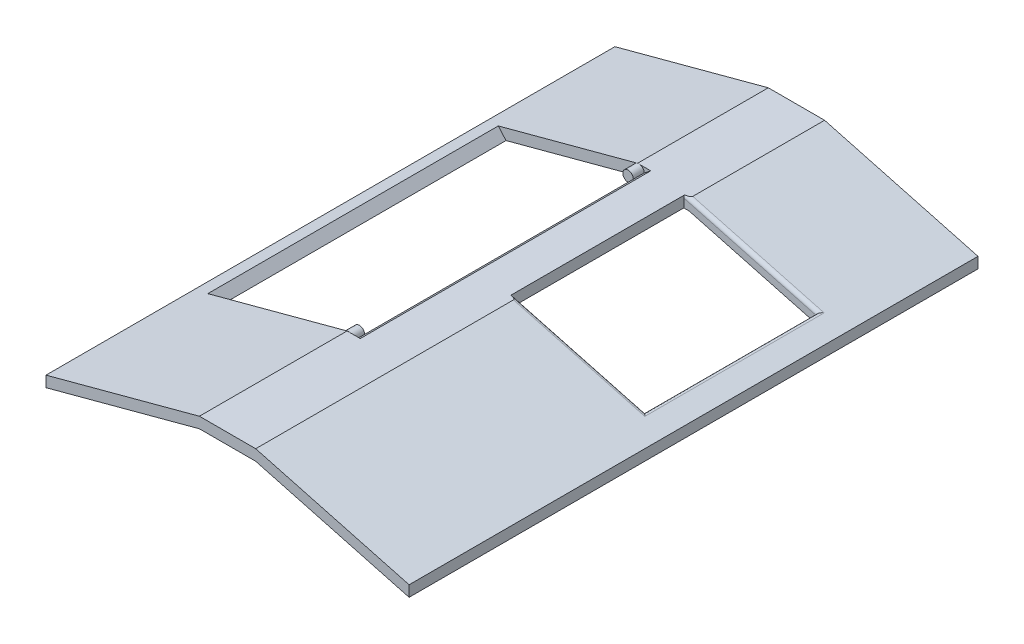
SolidWorks part; units mm, degrees
material "Titan"
ref_plane "Ebene vorne" through (0, 0, 0) normal (0, 0, 1) x (1, 0, 0)
ref_plane "Ebene oben" through (0, 0, 0) normal (0, 1, 0) x (1, 0, 0)
ref_plane "Ebene rechts" through (0, 0, 0) normal (1, 0, 0) x (0, 0, -1)
sketch "Skizze1" plane through (0, 0, 0) normal (0, 0, 1) x (1, 0, 0)
  line L0 (650.3605, 174.2211) -> (650.3605, 144.2211)
  line L5 (650.3605, 144.2211) -> (227.8605, 257.4296)
  line L6 (227.8605, 257.4296) -> (72.8605, 257.4296)
  line L7 (72.8605, 257.4296) -> (-349.6395, 144.2211)
  line L8 (-349.6395, 144.2211) -> (-349.6395, 174.2211)
  line L9 (-349.6395, 174.2211) -> (72.8605, 287.4296)
  line L10 (72.8605, 287.4296) -> (227.8605, 287.4296)
  line L11 (227.8605, 287.4296) -> (650.3605, 174.2211)
  point P0 (0, 0)
  point P7 (650.3605, 159.2211)
  dimension "D1" = 105
  dimension "D2" = 1000
  dimension "D3" = 155
  dimension "D4" = 30
extrude "Aufsatz-Linear austragen1" add sketch "Skizze1" along normal blind 1566.7
sketch "Skizze2" plane through (0, 287.4296, 0) normal (0, 1, 0) x (1, 0, 0)
  line L0 (227.8605, 0) -> (72.8605, 0) construction
  line L1 (145.3605, -360) -> (-289.4795, -360)
  line L2 (145.3605, -360) -> (145.3605, -1160)
  line L3 (145.3605, -1160) -> (-289.4795, -1160)
  line L4 (-289.4795, -360) -> (-289.4795, -1160)
  line L5 (150.3605, -3666.9697) -> (150.3605, -1453.7419) construction
  line L7 (213.1005, -373) -> (577.1205, -373)
  line L8 (213.1005, -373) -> (213.1005, -847)
  line L9 (213.1005, -847) -> (577.1205, -847)
  line L10 (577.1205, -373) -> (577.1205, -847)
  point P14 (150.3605, 0)
  dimension "D1" = 360
  dimension "D2" = 5
  dimension "D3" = 800
  dimension "D4" = 434.84
  dimension "D5" = 474
  dimension "D6" = 364.02
  dimension "D7" = 62.74
  dimension "D8" = 373
extrude "Schnitt-Linear austragen1" cut sketch "Skizze2" against normal up to next
chamfer "Fase1" distance 22 distance2 30 1 edges at (-289.4795, 190.3409, 760) first distance on face at (-123.3495, 234.8553, 771.675)
fillet "Verrundung1" radius 10 3 edges at (402.4905, 240.6377, 373) (577.1205, 193.8457, 610) (402.4905, 240.6377, 847)
sketch "Skizze4" plane through (0, 0, 1160) normal (0, 0, -1) x (-1, 0, 0)
  line L4 (-37.3835, 247.9236) -> (-108.3409, 266.9366) construction
  line L5 (-72.8605, 257.4296) -> (289.4795, 160.3409) construction
  line L8 (-72.8605, 287.4296) -> (-80.3605, 259.4392) construction
  circle A2 centre (-76.6105, 273.4344) radius 14.4889
extrude "Aufsatz-Linear austragen3" add sketch "Skizze4" along normal blind 30
sketch "Skizze6" plane through (0, 0, 360) normal (0, 0, 1) x (1, 0, 0)
  line L0 (57.1184, 253.2115) -> (89.5556, 261.9031) construction
  line L1 (-289.4795, 160.3409) -> (72.8605, 257.4296) construction
  line L2 (72.8605, 287.4296) -> (80.3605, 259.4392) construction
  line L5 (145.3605, 287.4296) -> (145.3605, 257.4296)
  line L6 (145.3605, 257.4296) -> (84.3562, 257.4296)
  line L7 (72.8605, 257.4296) -> (145.3605, 257.4296) construction
  line L8 (84.3562, 257.4296) -> (84.3562, 261.1897)
  line L9 (91.0994, 273.4344) -> (109.1105, 287.4296)
  line L10 (145.3605, 287.4296) -> (72.8605, 287.4296) construction
  line L11 (109.1105, 287.4296) -> (145.3605, 287.4296)
  arc A0 (80.3605, 259.4392) -> (72.8605, 287.4296) centre (76.6105, 273.4344) ccw construction
  arc A2 (91.0994, 273.4344) -> (84.3562, 261.1897) centre (76.6105, 273.4344) cw
  point P7 (76.6105, 273.4344)
extrude "Aufsatz-Linear austragen7" add sketch "Skizze6" along normal up to surface (800 mm away) up to face at (-11.9153, 241.9503, 1160)
pattern_linear "Lineares Muster2" count 2 spacing 770 along (0, 0, -1) of "Aufsatz-Linear austragen3"
